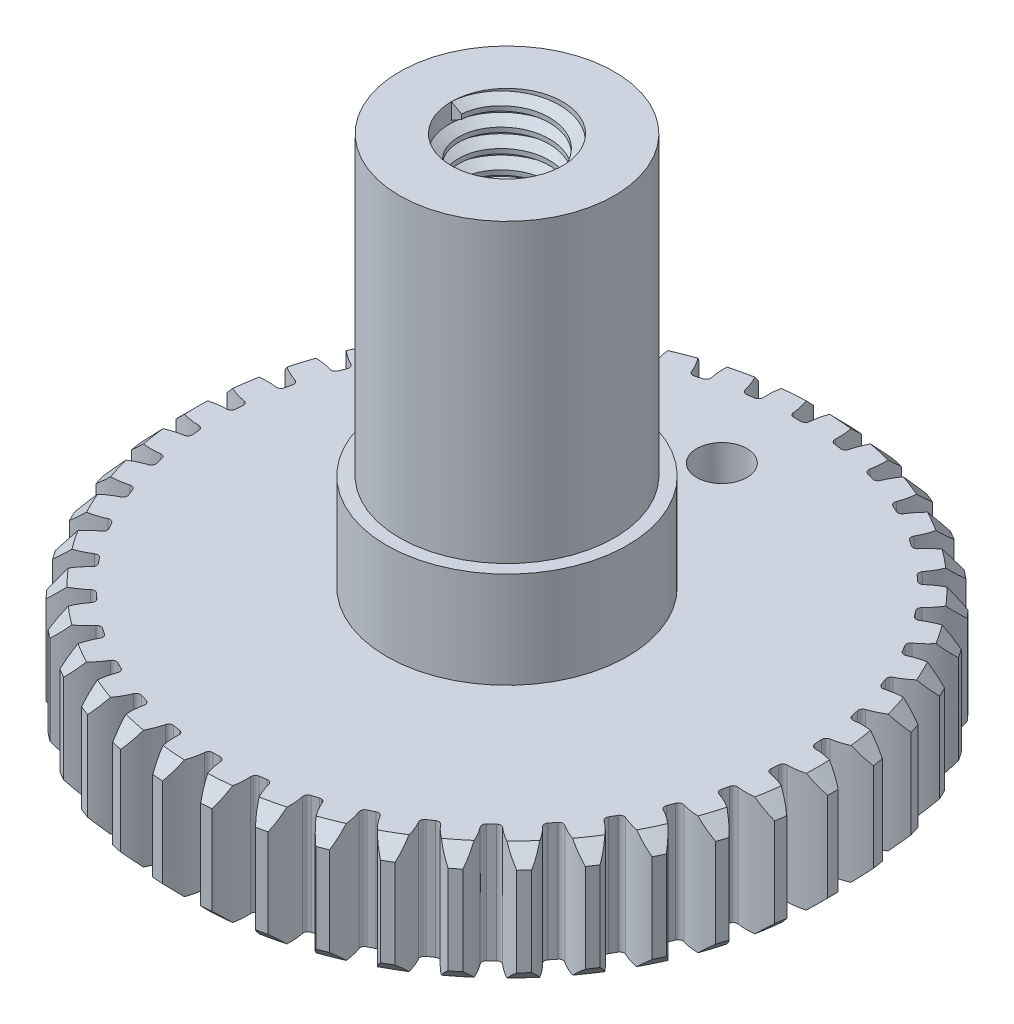
SolidWorks part; units mm, degrees
ref_plane "Front Plane" through (0, 0, 0) normal (0, 0, 1) x (1, 0, 0)
ref_plane "Top Plane" through (0, 0, 0) normal (0, 1, 0) x (1, 0, 0)
ref_plane "Right Plane" through (0, 0, 0) normal (1, 0, 0) x (0, 0, -1)
sketch "Sketch1" plane through (0, 0, 0) normal (0, 1, 0) x (1, 0, 0)
  circle A0 centre (0, 0) radius 8.4 construction
  circle A1 centre (0, 0) radius 8.8
  dimension "D1" = 16.8
  dimension "D2" = 17.6
extrude "Boss-Extrude1" add sketch "Sketch1" along normal blind 3.2
sketch "Sketch2" plane through (0, 3.2, 0) normal (0, 1, 0) x (1, 0, 0)
  line L0 (0, 8.8) -> (0, 0) construction
  line L1 (0, 0) -> (1.3116, 8.7017) construction
  line L2 (0, 0) -> (0.6576, 8.7754) construction
  line L3 (-0.2081, 7.8363) -> (0, 0) construction
  line L4 (-0.3141, 8.3941) -> (0.3141, 8.3941) construction
  line L5 (0.3141, 8.3941) -> (0.9405, 8.3472) construction
  line L6 (-0.4575, 8.7881) -> (0, 7.5312) construction
  circle A0 centre (0, 0) radius 8 construction
  circle A2 centre (0, 0) radius 8.8 construction
  arc A3 (-0.5144, 8.785) -> (-0.2081, 7.8363) centre (-1.9756, 7.7894) cw
  circle A4 centre (0, 0) radius 8.8 construction
  arc A5 (0.5144, 8.785) -> (0.2081, 7.8363) centre (1.9756, 7.7894) ccw
  circle A6 centre (0, 0) radius 8.4 construction
  arc A7 (0.2081, 7.8363) -> (-0.2081, 7.8363) centre (0, 0) ccw
  arc A8 (0.5144, 8.785) -> (-0.5144, 8.785) centre (0, 0) ccw
  dimension "D1" = 8.571
  dimension "D2" = 0.8
  dimension "D4" = 20
  dimension "D3" = 0.1609
extrude "Cut-Extrude1" cut sketch "Sketch2" against normal through all both and the other way through all
fillet "Fillet2" radius 0.12 2 edges at (0.2081, 1.6, -7.8363) (-0.2081, 1.6, -7.8363)
chamfer "Chamfer1" distance 0.4 2 edges at (0, 0, 8.8) (0, 3.2, 8.8)
pattern_circular "CirPattern3" count 42 over 360 about axis through (0, 3.2, 0) along (0, -1, 0) of "Fillet2", "Cut-Extrude1" reverse direction yes
sketch "Sketch3" plane through (0, 3.2, 0) normal (0, 1, 0) x (1, 0, 0)
  circle A0 centre (0, 0) radius 3.25
  dimension "D1" = 6.5
extrude "Boss-Extrude2" add sketch "Sketch3" along normal blind 2.6
sketch "Sketch4" plane through (0, 5.8, 0) normal (0, 1, 0) x (1, 0, 0)
  circle A0 centre (0, 0) radius 2.9
  circle A1 centre (0, 0) radius 1.5
  dimension "D1" = 5.8
  dimension "D2" = 3
extrude "Boss-Extrude3" add sketch "Sketch4" along normal blind 8
sketch "Sketch5" plane through (0, 0, 0) normal (0, -1, 0) x (-1, 0, 0)
  circle A0 centre (0, 0) radius 6
  dimension "D1" = 12
extrude "Boss-Extrude4" add sketch "Sketch5" along normal blind 0.9
sketch "Sketch6" plane through (0, -0.9, 0) normal (0, -1, 0) x (-1, 0, 0)
  circle A0 centre (0, 0) radius 5
  dimension "D1" = 10
extrude "Cut-Extrude2" cut sketch "Sketch6" against normal blind 2.6
sketch "Sketch7" plane through (0, 3.2, 0) normal (0, 1, 0) x (1, 0, 0)
  circle A0 centre (0, 5.8) radius 0.6784
  dimension "D1" = 5.8
extrude "Cut-Extrude3" cut sketch "Sketch7" against normal through all
sketch "Sketch8" plane through (0, 1.7, 0) normal (0, -1, 0) x (-1, 0, 0)
  line L1 (-1, 2.6) -> (1, 2.6)
  line L2 (-1, 2.6) -> (-1, -2.6)
  line L3 (-1, -2.6) -> (1, -2.6)
  line L4 (1, 2.6) -> (1, -2.6)
  line L5 (-1, 2.6) -> (1, -2.6) construction
  line L6 (-1, -2.6) -> (1, 2.6) construction
  point P0 (0, 0)
  dimension "D1" = 5.2
  dimension "D2" = 2
extrude "Cut-Extrude4" cut sketch "Sketch8" against normal blind 3
fillet "Fillet4" radius 0.8 4 edges at (1, 3.2, -2.6) (-1, 3.2, -2.6) (1, 3.2, 2.6) (-1, 3.2, 2.6)
thread "Thread1" pitch 0.5 method extrude profile "Thread Profile1" start angle 0, offset 0, length 0, pitch 0.5, diameter 3
ref_plane "Plane1" through (-1.5, 13.8, 0) normal (0, 0, 1) x (-1, 0, 0)
sketch "Thread Profile1" plane through (-1.5, 13.8, 0) normal (0, 0, 1) x (-1, 0, 0)
  line L0 (0, 0) -> (0, 0.5) construction
  line L11 (0, 0) -> (0, 0.4375)
  line L12 (0, 0.4375) -> (-0.2706, 0.2812)
  line L13 (-0.2706, 0.2812) -> (-0.2706, 0.1562)
  line L15 (-0.2706, 0.1562) -> (0, 0)
  line L17 (-0.2706, 0.2187) -> (0, 0.2187) construction
  point P2 (0, 0)
  dimension "Pitch" = 0.5
  dimension "Profile_Angle" = 60
  dimension "Profile_Land" = 0.125
  dimension "Profile_Height" = 0.2706
equation "\"Module\"= 0.4mm"
equation "\"Number of teeth\"= 42"
equation "\"Pressure Angle\"= 20"
equation "\"D1@Sketch1\"=\"Module\" * \"Number of teeth\""
equation "\"D2@Sketch1\"=(\"Number of teeth\" + 2) * \"Module\""
equation "\"D1@Sketch2\"=360 / \"Number of teeth\""
equation "\"D2@Sketch2\"=\"Module\" * 2"
equation "\"D4@Sketch2\"=\"Pressure Angle\""
equation "\"D1@Fillet2\"=0.3 * \"Module\""
equation "\"D1@CirPattern3\"=\"Number of teeth\""
equation "\"D1@Chamfer1\"=\"Module\""
